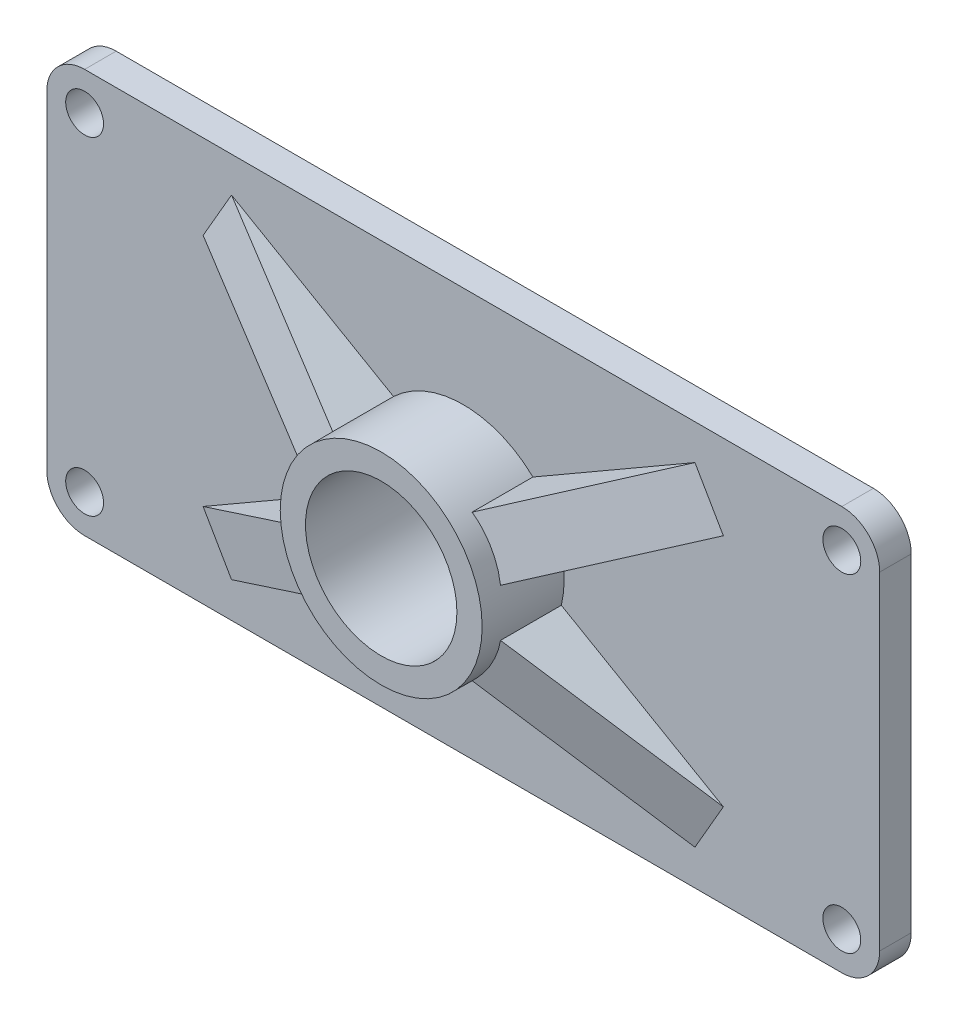
SolidWorks part; units mm, degrees
material "Thornel Mat VMA"
ref_plane "Front Plane" through (0, 0, 0) normal (0, 0, 1) x (1, 0, 0)
ref_plane "Top Plane" through (0, 0, 0) normal (0, 1, 0) x (1, 0, 0)
ref_plane "Right Plane" through (0, 0, 0) normal (1, 0, 0) x (0, 0, -1)
sketch "Sketch1" plane through (0, 0, 0) normal (0, 0, 1) x (1, 0, 0)
  line L1 (-60, -32) -> (60, -32)
  line L2 (-66, -26) -> (-66, 26)
  line L3 (-60, 32) -> (60, 32)
  line L4 (66, -26) -> (66, 26)
  line L5 (-66, -32) -> (66, 32) construction
  line L6 (-66, 32) -> (66, -32) construction
  arc A0 (60, 32) -> (66, 26) centre (60, 26) cw
  arc A1 (60, -32) -> (66, -26) centre (60, -26) ccw
  arc A2 (-60, -32) -> (-66, -26) centre (-60, -26) cw
  arc A3 (-66, 26) -> (-60, 32) centre (-60, 26) cw
  circle A4 centre (-60, -26) radius 3
  circle A5 centre (-60, 26) radius 3
  circle A6 centre (60, 26) radius 3
  circle A7 centre (60, -26) radius 3
  circle A8 centre (0, 0) radius 12
  point P0 (0, 0)
  dimension "D3" = 6
  dimension "D4" = 6
  dimension "D5" = 6
  dimension "D6" = 6
  dimension "D7" = 6
  dimension "D8" = 24
  dimension "D1" = 132
  dimension "D2" = 64
extrude "Boss-Extrude1" add sketch "Sketch1" along normal blind 5
sketch "Sketch2" plane through (0, 0, 5) normal (0, 0, 1) x (1, 0, 0)
  circle A0 centre (0, 0) radius 12 construction
  circle A1 centre (0, 0) radius 12
  circle A2 centre (0, 0) radius 16
  dimension "D1" = 32
extrude "Boss-Extrude2" add sketch "Sketch2" along normal blind 13
ref_axis "Axis1" through (0, 0, 18) along (0, 0, -1)
ref_plane "Plane4" through (0, 0, 0) normal (-0.5, -0.866, 0) x (0, 0, -1)
sketch "Sketch5" plane through (0, 0, 0) normal (-0.5, -0.866, 0) x (0, 0, -1)
  line L0 (-14.4227, 16) -> (-5, 45)
  line L1 (-5, 16) -> (-5, -16) construction
  line L2 (-5, 16) -> (-5, -16) construction
  line L3 (-5, 16) -> (-5, 56.0099) construction
  line L5 (-5, 16) -> (-18, 16) construction
  line L6 (-18, 0) -> (0, 0) construction
  dimension "D1" = 162
  dimension "D2" = 45
rib "Rib1" sketch "Sketch5" sketch "Sketch5" thickness 9 extrusion direction parallel to sketch draft on no parameters "D1"=9
pattern_circular "CirPattern1" count 2 over 360 about axis through (0, 0, 18) along (0, 0, 1) of "Rib1"
ref_plane "Plane5" through (0, 0, 0) normal (0.5, -0.866, 0) x (0, 0, -1)
mirror "Mirror1" about plane through (0, 0, 0) normal (0, 1, 0) of "CirPattern1"
